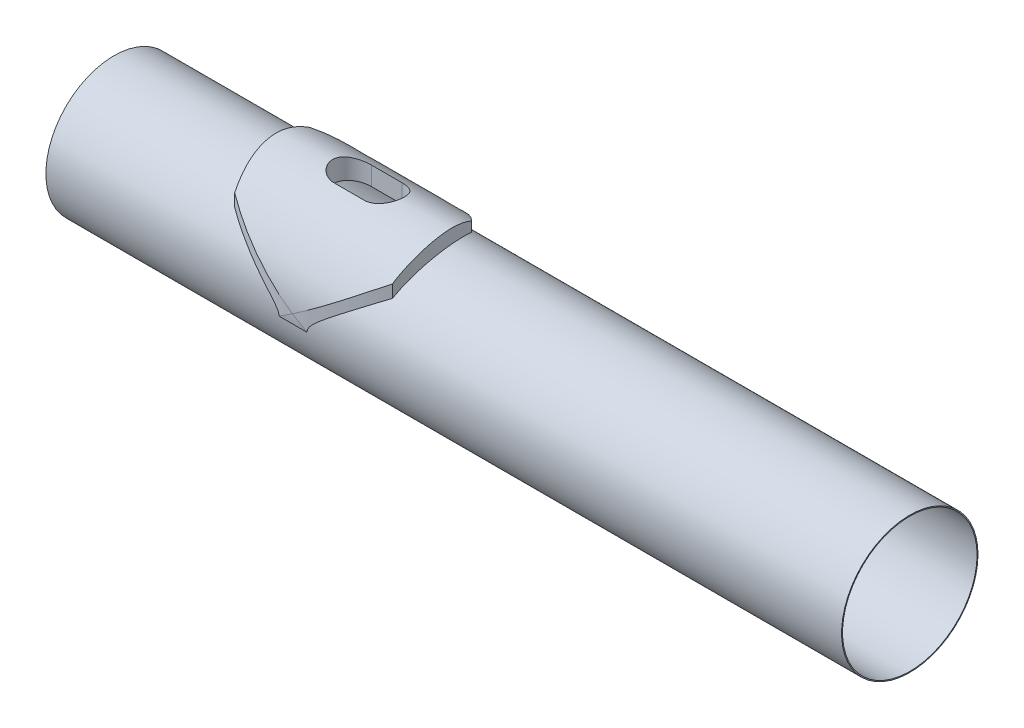
SolidWorks part; units mm, degrees
note: The reader was unsure of these and kept them because the rebuilt part matched: shared geometry of "Sketch7<4>", "Sketch2<3>".
material "Pure Silver"
ref_plane "Front Plane" through (0, 0, 0) normal (0, 0, 1) x (1, 0, 0)
ref_plane "Top Plane" through (0, 0, 0) normal (0, 1, 0) x (1, 0, 0)
ref_plane "Right Plane" through (0, 0, 0) normal (1, 0, 0) x (0, 0, -1)
sketch "Sketch1" plane through (0, 0, 0) normal (1, 0, 0) x (0, 0, -1)
  circle A0 centre (0, 0) radius 18
  circle A1 centre (0, 0) radius 17.75
  dimension "D1" = 36
  dimension "D2" = 35.5
extrude "Boss-Extrude1" add sketch "Sketch1" along normal blind 210
sketch "Sketch2" plane through (0, 0, 0) normal (0, 1, 0) x (1, 0, 0)
  line L0 (63, 0) -> (71, 0) construction
  line L1 (63, 5) -> (71, 5)
  line L2 (63, -5) -> (71, -5)
  line L3 (0, 18) -> (0, -18) construction
  line L4 (62.5, 0) -> (71.5, 0) construction
  line L5 (62.5, 5.5) -> (71.5, 5.5)
  line L6 (62.5, -5.5) -> (71.5, -5.5)
  arc A0 (63, 5) -> (63, -5) centre (63, 0) ccw
  arc A1 (71, -5) -> (71, 5) centre (71, 0) ccw
  arc A2 (62.5, 5.5) -> (62.5, -5.5) centre (62.5, 0) ccw
  arc A3 (71.5, -5.5) -> (71.5, 5.5) centre (71.5, 0) ccw
  point P2 (67, 0)
  point P12 (67, 0)
  dimension "D5" = 0.5
  dimension "D6" = 0.5
  dimension "D1" = 67
  dimension "D2" = 8
  dimension "D3" = 10
  dimension "D4" = 11
ref_plane "Plane1" through (0, 0, 0) normal (-1, 0, 0) x (0, 0, 1)
ref_plane "Plane2" through (67, 0, 0) normal (-1, 0, 0) x (0, 0, 1)
sketch "Sketch4" plane through (67, 0, 0) normal (-1, 0, 0) x (0, 0, 1)
  arc A0 (-13.7799, 14.1774) -> (19.7709, 0) centre (0, 0) cw
  spline S0 degree 3 poles (-13.7799, 14.1774) (-10.6858, 18.6127) (-3.1797, 24.8811) (14.2454, 21.1776) (20.9387, 8.5506) (19.7709, 0) knots 0 0 0 0 0.33128 0.485624 1 1 1 1
extrude "Boss-Extrude2" add sketch "Sketch4" along normal mid plane 45 separate body
extrude "Cut-Extrude2" cut sketch "Sketch2" along normal through all contours L2 A1 L1 A0
ref_plane "Plane3" through (0, 27, 0) normal (0, 1, 0) x (1, 0, 0)
sketch "Sketch6" [suppressed] plane through (0, 27, 0) normal (0, 1, 0) x (1, 0, 0)
  line L0 (56.8683, -19.3191) -> (76.2463, -19.3191)
  line L1 (44.5, 13.7799) -> (89.5, 13.7799)
  line L2 (44.5, 13.7799) -> (44.5, -19.9356)
  line L3 (44.5, -19.9356) -> (89.5, -19.9356)
  line L4 (89.5, 13.7799) -> (89.5, -19.9356)
  line L5 (67, 19.525) -> (67, -19.525) construction
  line L6 (44.5, -19.9356) -> (89.5, -19.9356) construction
  arc A0 (67, 13.7799) -> (89.9614, 5.2677) centre (67.8726, -19.0909) cw
  arc A1 (67, 13.7799) -> (45.7838, 5.2677) centre (67.8726, -19.0909) ccw
  arc A2 (45.7838, 5.2677) -> (56.8683, -19.3191) centre (74.0659, 3.2261) ccw
  arc A3 (89.9614, 5.2677) -> (76.2463, -19.3191) centre (61.6073, 4.9655) cw
  arc A4 (54.2756, -17.0812) -> (79.2123, -17.263) centre (67, 17.9581) ccw
  point P12 (66.7283, -19.3191)
  point P15 (67, 13.7799)
sketch "Sketch7" plane through (0, 27, 0) normal (0, 1, 0) x (1, 0, 0)
  line L0 (67, 19.525) -> (67, -19.525) construction
  line L1 (44.5, -19.9356) -> (89.5, -19.9356) construction
  line L2 (44.5, 13.7799) -> (44.5, -19.9356) construction
  line L4 (44.5, 13.7799) -> (89.5, 13.7799) construction
  line L5 (44.5, 13.7799) -> (89.5, 13.7799)
  line L6 (44.5, 13.7799) -> (44.5, -19.9356)
  line L7 (44.5, -19.9356) -> (89.5, -19.9356)
  line L8 (89.5, 13.7799) -> (89.5, -19.9356)
  arc A0 (46.1855, -14.3556) -> (87.8145, -14.3556) centre (67, 21.6759) ccw
  arc A1 (67, 13.7799) -> (45.6224, 5.9881) centre (64.5092, -12.608) ccw
  arc A2 (45.6224, 5.9881) -> (46.1855, -14.3556) centre (82.4436, -3.1724) ccw
  arc A3 (88.3776, 5.9881) -> (87.8145, -14.3556) centre (51.5564, -3.1724) cw
  arc A4 (67, 13.7799) -> (88.3776, 5.9881) centre (69.4908, -12.608) cw
extrude "Cut-Extrude12" cut sketch "Sketch7" against normal up to next contours A2 L6 L7 A0 | L8 A3 A0 L7
extrude "Cut-Extrude13" cut sketch "Sketch7<4>" against normal up to body separate body contours A2 A1 L5 L6 | L5 A4 A3 L8
sketch "Sketch7<4>" plane through (0, 27, 0) normal (0, 1, 0) x (1, 0, 0) same geometry as "Sketch7"
extrude "Boss-Extrude3" add sketch "Sketch2<3>" against normal up to body from offset 21 contours L6 A3 L5 A2 A1 L2 A0 L1
sketch "Sketch2<3>" plane through (0, 0, 0) normal (0, 1, 0) x (1, 0, 0) same geometry as "Sketch2"
extrude "Cut-Extrude10" [suppressed] cut sketch "Sketch6" against normal up to next separate body contours A2 L2 L3 | L4 A3 L3
